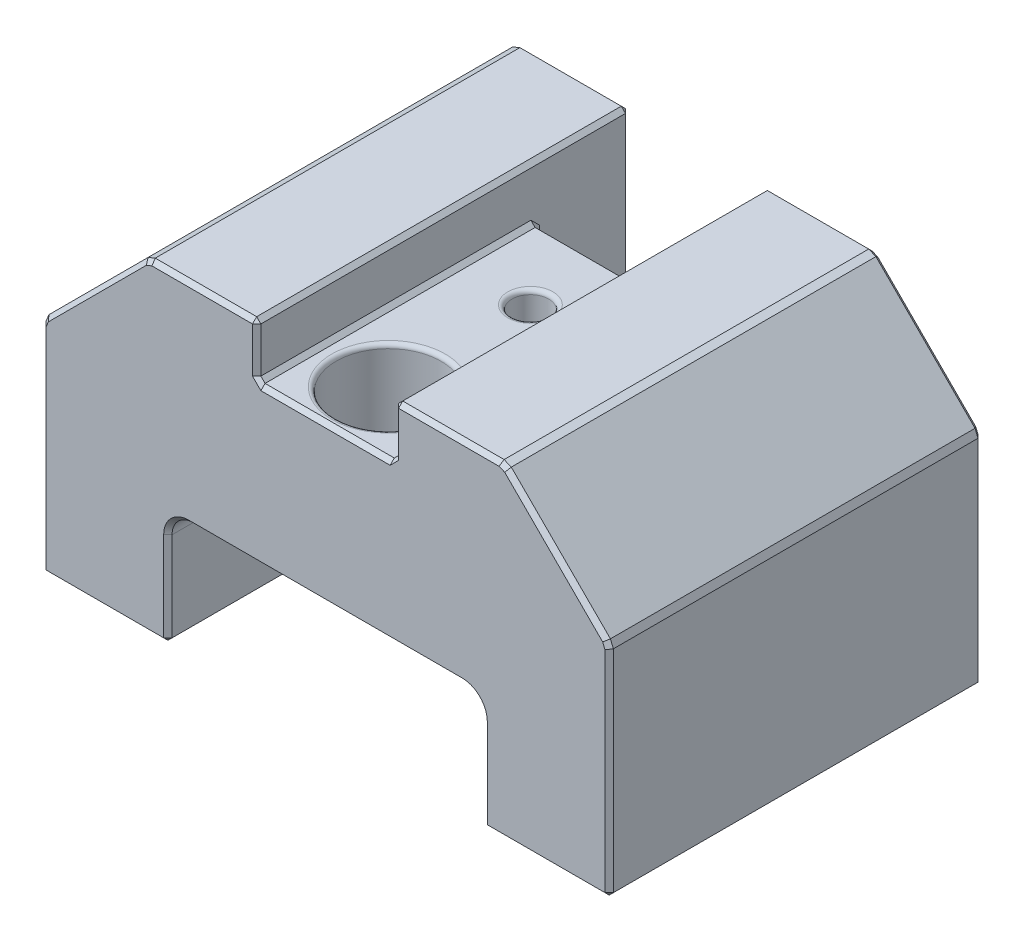
SolidWorks part; units mm, degrees
note: The reader was unsure of these and kept them because the rebuilt part matched: shared geometry of "Sketch1<9>", "Sketch1<4>", "Sketch6<4>".
ref_plane "Front Plane" through (0, 0, 0) normal (0, 0, 1) x (1, 0, 0)
ref_plane "Top Plane" through (0, 0, 0) normal (0, 1, 0) x (1, 0, 0)
ref_plane "Right Plane" through (0, 0, 0) normal (1, 0, 0) x (0, 0, -1)
sketch "Sketch1" plane through (0, 0, 0) normal (0, 0, 1) x (1, 0, 0)
  line L0 (0, 45.3438) -> (0, 0) construction
  line L1 (0, 0) -> (45.3438, 0) construction
  line L2 (-15, 4.1) -> (15, 4.1) construction
  line L3 (-12.5, 15) -> (12.5, 15) construction
  line L4 (-15, 12.5) -> (-15, -12.5) construction
  line L5 (-12.5, -15) -> (12.5, -15) construction
  line L6 (15, 12.5) -> (15, -12.5) construction
  line L7 (-15, -4.1) -> (15, -4.1) construction
  line L8 (-15, -12.5) -> (-15, 13)
  line L9 (-13, 15) -> (13, 15)
  line L10 (15, 13) -> (15, -12.5)
  line L11 (15, -12.5) -> (27, -12.5)
  line L12 (27, -12.5) -> (27, 35)
  line L13 (27, 35) -> (-27, 35)
  line L14 (-27, 35) -> (-27, -12.5)
  line L15 (-27, -12.5) -> (-15, -12.5)
  line L16 (6.55, 29.9) -> (6.55, 20.1)
  line L17 (-6.55, 20.1) -> (6.55, 20.1)
  line L18 (-6.55, 20.1) -> (-6.55, 15)
  line L19 (-6.55, 15) -> (6.55, 15)
  line L20 (6.55, 20.1) -> (6.55, 15)
  line L21 (-6.55, 35) -> (6.55, 35)
  line L22 (-6.55, 35) -> (-6.55, 29.9)
  line L23 (-6.55, 29.9) -> (6.55, 29.9)
  line L24 (6.55, 35) -> (6.55, 29.9)
  line L25 (-6.55, 29.9) -> (-6.55, 20.1)
  line L26 (-15, 4.1) -> (-27, 4.1)
  line L27 (15, 4.1) -> (27, 4.1)
  arc A0 (-15, -12.5) -> (-12.5, -15) centre (-12.5, -12.5) ccw construction
  arc A1 (12.5, -15) -> (15, -12.5) centre (12.5, -12.5) ccw construction
  arc A2 (15, 12.5) -> (12.5, 15) centre (12.5, 12.5) ccw construction
  arc A3 (-12.5, 15) -> (-15, 12.5) centre (-12.5, 12.5) ccw construction
  arc A4 (15, 13) -> (13, 15) centre (13, 13) ccw
  arc A5 (-13, 15) -> (-15, 13) centre (-13, 13) ccw
  point P10 (-15, -15)
  point P13 (15, -15)
  point P18 (-15, 15)
  point P33 (-15, 15)
  dimension "D3" = 2.5
  dimension "D5" = 2
  dimension "D1" = 30
  dimension "D2" = 30
  dimension "D4" = 8.2
  dimension "D6" = 12
  dimension "D7" = 20
  dimension "D8" = 5.1
  dimension "D9" = 5.1
  dimension "D10" = 13.1
extrude "Boss-Extrude1" add sketch "Sketch1" along normal blind 23 contours A4 L10 L11 L12 L13 L24 L16 L20 L9 | A5 L9 L18 L25 L22 L13 L14 L15 L8 | L23 L25 L17 L16
extrude "Boss-Extrude5" add sketch "Sketch1<9>" along normal blind 12.5 from surface at 23 contours A5 L9 L18 L25 L22 L13 L14 L26 L8 | L23 L25 L17 L16 | A4 L10 L27 L12 L13 L24 L16 L20 L9 | L20 L17 L18 L9 starting at face at (0, 19.0682, 23)
sketch "Sketch1<9>" plane through (0, 0, 0) normal (0, 0, 1) x (1, 0, 0) same geometry as "Sketch1"
extrude "Cut-Extrude1" cut sketch "Sketch1<4>" along normal blind 9 contours L23 L25 L17 L16
sketch "Sketch1<4>" plane through (0, 0, 0) normal (0, 0, 1) x (1, 0, 0) same geometry as "Sketch1"
chamfer "Chamfer4" distance 10 angle 45 2 edges at (27, 35, 17.75) (-27, 35, 17.75)
chamfer "Chamfer6" distance 0.4 4 edges at (-27, 25, 17.75) (-17, 35, 17.75) (17, 35, 17.75) (27, 25, 17.75)
sketch "Sketch6" plane through (0, 29.9, 0) normal (0, 1, 0) x (1, 0, 0)
  line L0 (0, 0) -> (0, -35.5) construction
  line L1 (6.55, -35.5) -> (-6.55, -35.5) construction
  circle A0 centre (0, -16) radius 1.75
  circle A1 centre (0, -29.5) radius 5
  circle A2 centre (0, -29.5) radius 2.55
  dimension "D1" = 16
  dimension "D2" = 3.5
  dimension "D4" = 10
  dimension "D5" = 5.1
  dimension "D3" = 6
extrude "Cut-Extrude5" cut sketch "Sketch6" against normal through all contours A0 L0 | L0 A0 | L0 A2 | A2 L0
extrude "Cut-Extrude6" cut sketch "Sketch6<4>" against normal blind 12
sketch "Sketch6<4>" plane through (0, 29.9, 0) normal (0, 1, 0) x (1, 0, 0) same geometry as "Sketch6"
chamfer "Chamfer7" distance 0.4 angle 45 59 edges at (0, 15, 23) (-27, 4.1, 17.75) (-15, 4.1, 17.75) (15, 4.1, 17.75) (27, 4.1, 17.75) (6.55, 35, 17.75) (6.55, 29.9, 22.25) (6.55, 25, 0) (11.575, 35, 35.5) (11.575, 35, 0) (16.9414, 34.8586, 35.5) (16.9414, 34.8586, 0) (22, 30, 0) (22, 30, 35.5) (26.8586, 24.9414, 0) (26.8586, 24.9414, 35.5) (27, 14.35, 0) (27, 14.35, 35.5) (21, 4.1, 0) (21, 4.1, 35.5) (15, 8.55, 0) (15, 8.55, 35.5) (14.4142, 14.4142, 0) (14.4142, 14.4142, 35.5) (9.775, 15, 0) (6.55, 15, 11.5) (6.55, 17.55, 23) (6.55, 20.1, 16) (-6.55, 15, 11.5) (-6.55, 17.55, 23) (-6.55, 20.1, 16) (-6.55, 25, 9) (0, 20.1, 9) (6.55, 25, 9) (0, 29.9, 9) (-6.55, 29.9, 22.25) (-21, 4.1, 0) (-21, 4.1, 35.5) (-15, 8.55, 0) (-15, 8.55, 35.5) (-14.4142, 14.4142, 0) (-14.4142, 14.4142, 35.5) (-9.775, 15, 0) (-6.55, 25, 0) (-27, 14.35, 35.5) (-27, 14.35, 0) (-26.8586, 24.9414, 35.5) (-26.8586, 24.9414, 0) (-22, 30, 0) (-22, 30, 35.5) (-16.9414, 34.8586, 0) (-16.9414, 34.8586, 35.5) (-11.575, 35, 0) (-11.575, 35, 35.5) (-6.55, 35, 17.75) (-6.55, 32.45, 35.5) (0, 29.9, 35.5) (6.55, 32.45, 35.5) (0, 15, 35.5)
fillet "Fillet1" radius 0.4 6 edges at (-2.55, 15, 29.5) (0, 20.1, 17.75) (0, 17.9, 32.05) (0, 17.9, 34.5) (0, 29.9, 17.75) (0, 29.9, 34.5)
